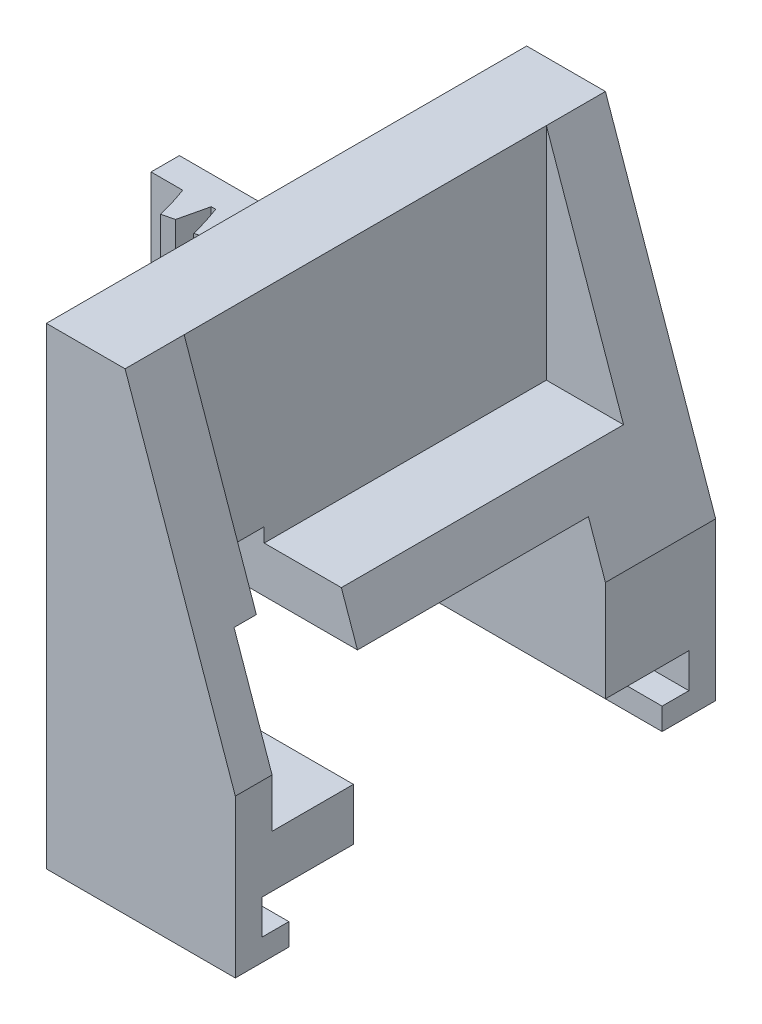
SolidWorks part; units mm, degrees
ref_plane "Front Plane" through (0, 0, 0) normal (0, 0, 1) x (1, 0, 0)
ref_plane "Top Plane" through (0, 0, 0) normal (0, 1, 0) x (1, 0, 0)
ref_plane "Right Plane" through (0, 0, 0) normal (1, 0, 0) x (0, 0, -1)
sketch "Sketch1" plane through (0, 0, 0) normal (0, 0, 1) x (1, 0, 0)
  line L0 (0, 0) -> (0, -30)
  line L1 (0, -30) -> (12, -30)
  line L2 (12, -30) -> (12, -20)
  line L3 (12, -20) -> (5, 0)
  line L4 (5, 0) -> (0, 0)
  dimension "D1" = 30
  dimension "D2" = 12
  dimension "D3" = 10
  dimension "D4" = 5
extrude "Boss-Extrude1" add sketch "Sketch1" against normal blind 30.5
sketch "Sketch4" plane through (0, 0, 0) normal (-1, 0, 0) x (0, 0, 1)
  line L0 (-30.5, 0) -> (-30.5, -30) construction
  line L1 (-23.5, -16.9179) -> (-7.5, -16.9179)
  line L2 (-23.5, -16.9179) -> (-23.5, -30.9179)
  line L3 (-23.5, -30.9179) -> (-7.5, -30.9179)
  line L4 (-7.5, -16.9179) -> (-7.5, -30.9179)
  point P4 (-23.5, -23.9179)
  dimension "D1" = 16
  dimension "D2" = 14
  dimension "D3" = 7
extrude "Cut-Extrude2" cut sketch "Sketch4" against normal blind 25 contours L2 L1 L4 L3
ref_plane "Plane1" through (0, 0, -15.25) normal (0, 0, 1) x (1, 0, 0)
sketch "Sketch6" plane through (0, 0, -15.25) normal (0, 0, 1) x (1, 0, 0)
  line L0 (5, 0) -> (5, -14)
  line L1 (5, -14) -> (9.9, -14)
  line L2 (12, -20) -> (5, 0) construction
  line L3 (9.9, -14) -> (5, 0)
  dimension "D1" = 14
extrude "Cut-Extrude4" cut sketch "Sketch6" against normal mid plane 23
ref_plane "Plane2" through (0, -22, 0) normal (0, 1, 0) x (1, 0, 0)
sketch "Sketch7" plane through (0, -22, 0) normal (0, 1, 0) x (1, 0, 0)
  line L0 (0, 27.45) -> (-19, 27.45)
  line L1 (0, 30.5) -> (0, 0) construction
  line L3 (0, 27.45) -> (0, 25.65)
  line L4 (0, 25.65) -> (-0.5, 25.65)
  line L47 (-0.5, 25.65) -> (-0.9304, 23.8151)
  line L62 (-6.6, 15.25) -> (6.6, 15.25) construction
  line L108 (-19, 25.65) -> (-19, 27.45)
  line L112 (-0.9304, 23.8151) -> (-1.6865, 23.6276)
  line L113 (-2.3144, 25.65) -> (-2.597, 25.65)
  line L114 (-3.0274, 23.8151) -> (-3.7835, 23.6276)
  line L115 (-2.597, 25.65) -> (-3.0274, 23.8151)
  line L116 (-5.1244, 23.8151) -> (-5.8805, 23.6276)
  line L117 (-4.694, 25.65) -> (-5.1244, 23.8151)
  line L118 (-7.2214, 23.8151) -> (-7.9775, 23.6276)
  line L119 (-6.791, 25.65) -> (-7.2214, 23.8151)
  line L120 (-9.3184, 23.8151) -> (-10.0745, 23.6276)
  line L121 (-8.888, 25.65) -> (-9.3184, 23.8151)
  line L122 (-11.4154, 23.8151) -> (-12.1715, 23.6276)
  line L123 (-10.985, 25.65) -> (-11.4154, 23.8151)
  line L124 (-13.5124, 23.8151) -> (-14.2685, 23.6276)
  line L125 (-13.082, 25.65) -> (-13.5124, 23.8151)
  line L126 (-4.4114, 25.65) -> (-4.694, 25.65)
  line L127 (-6.5085, 25.65) -> (-6.791, 25.65)
  line L128 (-8.6055, 25.65) -> (-8.888, 25.65)
  line L129 (-10.7025, 25.65) -> (-10.985, 25.65)
  line L130 (-12.7995, 25.65) -> (-13.082, 25.65)
  line L132 (-15.6094, 23.8151) -> (-16.3655, 23.6276)
  line L133 (-15.179, 25.65) -> (-15.6094, 23.8151)
  line L134 (-14.8965, 25.65) -> (-15.179, 25.65)
  line L135 (-16.9935, 25.65) -> (-19, 25.65)
  arc A0 (-1.6865, 23.6276) -> (-2.3144, 25.65) centre (-19.4305, 19.2266) ccw
  arc A1 (-3.7835, 23.6276) -> (-4.4114, 25.65) centre (-21.5275, 19.2266) ccw
  arc A2 (-5.8805, 23.6276) -> (-6.5085, 25.65) centre (-23.6245, 19.2266) ccw
  arc A3 (-7.9775, 23.6276) -> (-8.6055, 25.65) centre (-25.7215, 19.2266) ccw
  arc A4 (-10.0745, 23.6276) -> (-10.7025, 25.65) centre (-27.8185, 19.2266) ccw
  arc A5 (-12.1715, 23.6276) -> (-12.7995, 25.65) centre (-29.9155, 19.2266) ccw
  arc A6 (-14.2685, 23.6276) -> (-14.8965, 25.65) centre (-32.0125, 19.2266) ccw
  arc A7 (-16.3655, 23.6276) -> (-16.9935, 25.65) centre (-34.1095, 19.2266) ccw
  dimension "D1" = 7
  dimension "D4" = 8
  dimension "D2" = 19
  dimension "D3" = 1.8
  dimension "D6" = 0.5
  dimension "D7" = 12.2
extrude "Boss-Extrude2" add sketch "Sketch7" along normal blind 8
sketch "Sketch8" plane through (0, 0, 0) normal (-1, 0, 0) x (0, 0, 1)
  line L0 (-8.8338, -13.1) -> (-2.3338, -13.1)
  line L2 (-7.5, -30) -> (0, -30) construction
  line L6 (-2.3338, -13.1) -> (-2.3338, -23.1)
  line L7 (-2.3338, -23.1) -> (-8.8338, -23.1)
  line L9 (-8.8338, -23.1) -> (-8.8338, -13.1)
  dimension "D1" = 6.5
  dimension "D2" = 10
  dimension "D3" = 6.9
extrude "Cut-Extrude5" cut sketch "Sketch8" against normal through all
sketch "Sketch9" plane through (0, 0, 0) normal (-1, 0, 0) x (0, 0, 1)
  line L0 (-7.5, -26.4) -> (-1.7, -26.4)
  line L1 (-7.5, -23.1) -> (-7.5, -30) construction
  line L2 (-1.7, -26.4) -> (-1.7, -28.6)
  line L3 (-1.7, -28.6) -> (-3.4, -28.6)
  line L4 (-3.4, -28.6) -> (-3.4, -30.2967)
  line L5 (-3.4, -30.2967) -> (-7.5, -30.2967)
  line L6 (-7.5, -30.2967) -> (-7.5, -26.4)
  line L7 (-7.5, -30) -> (0, -30) construction
  line L8 (-15.25, -16.5) -> (-15.25, 16.5) construction
  line L9 (-23, -30.2967) -> (-23, -26.4)
  line L10 (-27.1, -30.2967) -> (-23, -30.2967)
  line L11 (-27.1, -28.6) -> (-27.1, -30.2967)
  line L12 (-28.8, -28.6) -> (-27.1, -28.6)
  line L13 (-28.8, -26.4) -> (-28.8, -28.6)
  line L14 (-23, -26.4) -> (-28.8, -26.4)
  dimension "D1" = 5.8
  dimension "D2" = 2.2
  dimension "D3" = 1.4
  dimension "D4" = 1.7
extrude "Cut-Extrude6" cut sketch "Sketch9" against normal through all
